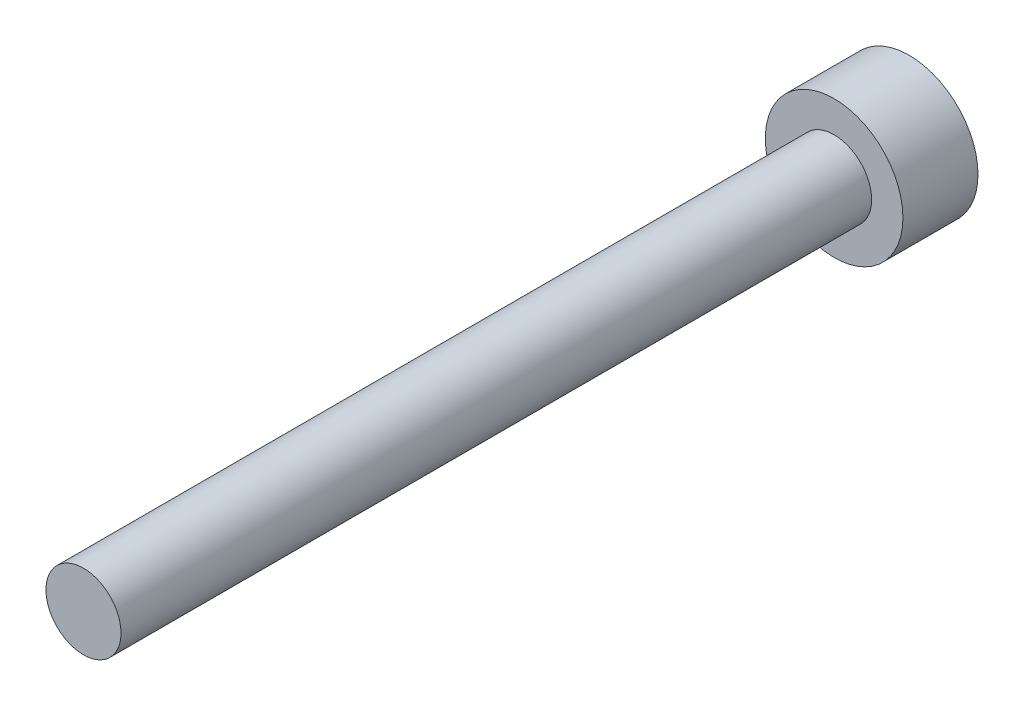
SolidWorks part; units mm, degrees
ref_plane "Front Plane" through (0, 0, 0) normal (0, 0, 1) x (1, 0, 0)
ref_plane "Top Plane" through (0, 0, 0) normal (0, 1, 0) x (1, 0, 0)
ref_plane "Right Plane" through (0, 0, 0) normal (1, 0, 0) x (0, 0, -1)
sketch "S01 - Head" plane through (0, 0, 0) normal (0, 0, 1) x (1, 0, 0)
  circle A0 centre (0, 0) radius 2.75
  dimension "D1" = 5.5
extrude "01 - Head" add sketch "S01 - Head" along normal blind 3 from offset 3 offset against normal yes
sketch "S02 - Nominal shank" plane through (0, 0, 0) normal (0, 0, 1) x (1, 0, 0)
  circle A0 centre (0, 0) radius 1.5
  dimension "D1" = 3
extrude "02 - Nominal shank" add sketch "S02 - Nominal shank" along normal blind 30
sketch "S03 - Hex key socket" plane through (0, 0, 0) normal (0, 0, 1) x (1, 0, 0)
  line L0 (1.4434, 0) -> (0.7217, 1.25)
  line L1 (0.7217, 1.25) -> (-0.7217, 1.25)
  line L2 (-0.7217, 1.25) -> (-1.4434, 0)
  line L3 (-1.4434, 0) -> (-0.7217, -1.25)
  line L4 (-0.7217, -1.25) -> (0.7217, -1.25)
  line L5 (0.7217, -1.25) -> (1.4434, 0)
  dimension "D1" = 0.7217
  dimension "D2" = 1.4434
  dimension "D3" = 0.7217
  dimension "D4" = 1.4434
  dimension "D5" = 1.25
  dimension "D6" = 1.25
extrude "03 - Hex key socket" cut sketch "S03 - Hex key socket" along normal blind 1.75 from offset 3.1 offset against normal yes
